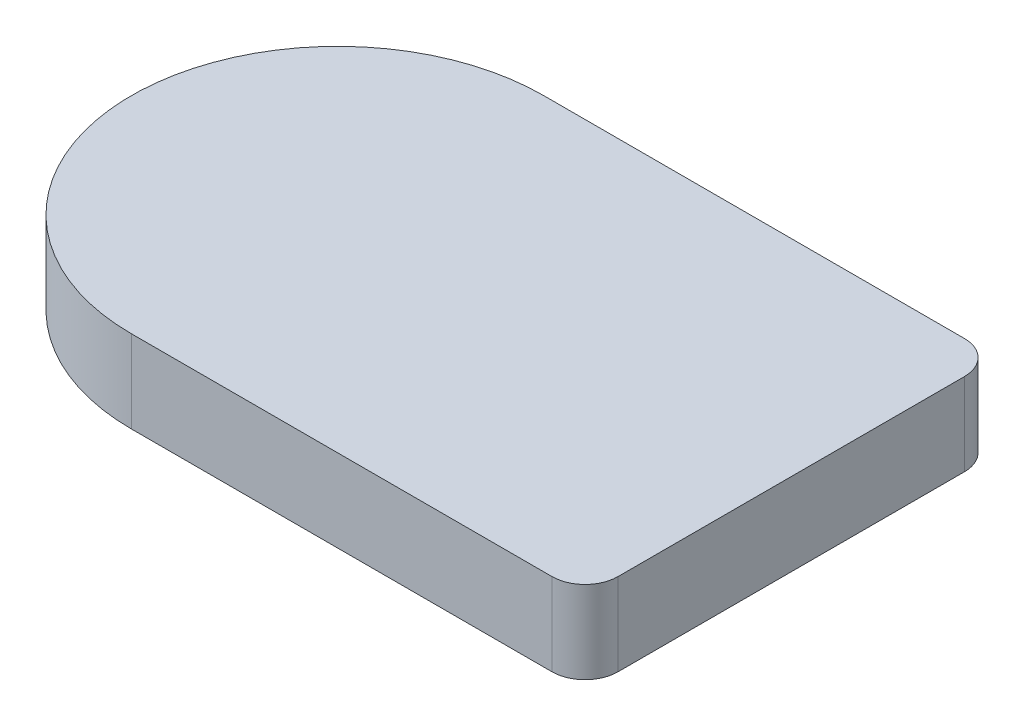
SolidWorks part; units mm, degrees
ref_plane "Front Plane" through (0, 0, 0) normal (0, 0, 1) x (1, 0, 0)
ref_plane "Top Plane" through (0, 0, 0) normal (0, 1, 0) x (1, 0, 0)
ref_plane "Right Plane" through (0, 0, 0) normal (1, 0, 0) x (0, 0, -1)
sketch "Sketch1" plane through (0, 0, 0) normal (0, 1, 0) x (1, 0, 0)
  line L1 (-20, -12.5) -> (20, -12.5)
  line L2 (-20, -12.5) -> (-20, 12.5)
  line L3 (-20, 12.5) -> (20, 12.5)
  line L4 (20, -12.5) -> (20, 12.5)
  line L5 (-20, -12.5) -> (20, 12.5) construction
  line L6 (-20, 12.5) -> (20, -12.5) construction
  point P0 (0, 0)
  dimension "D1" = 25
  dimension "D2" = 40
extrude "Boss-Extrude1" add sketch "Sketch1" along normal blind 5
sketch "Sketch2" plane through (0, 5, 0) normal (0, 1, 0) x (1, 0, 0)
  line L0 (0, 0) -> (-20, 0) construction
  line L1 (-20, 12.5) -> (-20, -12.5) construction
  line L6 (20, -12.5) -> (20, 12.5)
  line L7 (20, 12.5) -> (-20, 12.5)
  line L8 (-20, 12.5) -> (-20, -12.5)
  line L9 (-20, -12.5) -> (20, -12.5)
  line L10 (20, -12.5) -> (20, 12.5)
  line L11 (20, 12.5) -> (-20, 12.5)
  line L12 (-20, 12.5) -> (-20, -12.5)
  line L13 (-20, -12.5) -> (20, -12.5)
  circle A0 centre (-7.5, 0) radius 12.5
  point P5 (-7.5, 0)
  line M8 (-20, 12.5) -> (-20, -12.5)
  line M9 (-20, -12.5) -> (20, -12.5)
  dimension "D1" = 12.5
  dimension "D2" = 0
extrude "Cut-Extrude1" cut sketch "Sketch2" against normal through all contours A0 L11 M8 | A0 L12 M9 region at (-17.2079, 5, 9.7079) region at (-17.2079, 5, -9.7079)
fillet "Fillet1" radius 2 2 edges at (20, 2.5, 12.5) (20, 2.5, -12.5)
sketch "Sketch3" plane through (0, 0, 0) normal (0, -1, 0) x (1, 0, 0)
  line L0 (20, 0) -> (-20, 0) construction
  line L1 (20, 10.5) -> (20, -10.5) construction
  line L2 (0, -7.8582) -> (0, 7.8582)
  arc A0 (-7.5, 12.5) -> (-7.5, -12.5) centre (-7.5, 0) ccw construction
  circle A1 centre (-1.27, 0) radius 0.5
  circle A2 centre (-3.81, 0) radius 0.5
  circle A3 centre (-6.35, 0) radius 0.5
  circle A4 centre (-3.81, 2.54) radius 0.5
  circle A5 centre (-6.35, 2.54) radius 0.5
  circle A6 centre (-3.81, 5.08) radius 0.5
  circle A7 centre (-6.35, 5.08) radius 0.5
  circle A8 centre (-1.27, 2.54) radius 0.5
  circle A9 centre (-1.27, 5.08) radius 0.5
  circle A10 centre (1.27, 0) radius 0.5
  circle A11 centre (3.81, 0) radius 0.5
  circle A12 centre (6.35, 0) radius 0.5
  circle A13 centre (6.35, 2.54) radius 0.5
  circle A14 centre (3.81, 2.54) radius 0.5
  circle A15 centre (1.27, 2.54) radius 0.5
  circle A16 centre (1.27, 5.08) radius 0.5
  circle A17 centre (3.81, 5.08) radius 0.5
  circle A18 centre (6.35, 5.08) radius 0.5
  circle A19 centre (-6.35, -2.54) radius 0.5
  circle A20 centre (-6.35, -5.08) radius 0.5
  circle A21 centre (-3.81, -5.08) radius 0.5
  circle A22 centre (-1.27, -5.08) radius 0.5
  circle A23 centre (1.27, -5.08) radius 0.5
  circle A24 centre (3.81, -5.08) radius 0.5
  circle A25 centre (6.35, -5.08) radius 0.5
  circle A26 centre (6.35, -2.54) radius 0.5
  circle A27 centre (1.27, -2.54) radius 0.5
  circle A28 centre (-3.81, -2.54) radius 0.5
  circle A29 centre (-1.27, -2.54) radius 0.5
  circle A30 centre (3.81, -2.54) radius 0.5
  point P29 (0, 0)
  dimension "D1" = 1.27
  dimension "D2" = 1
  dimension "D3" = 3
  dimension "D4" = 3
